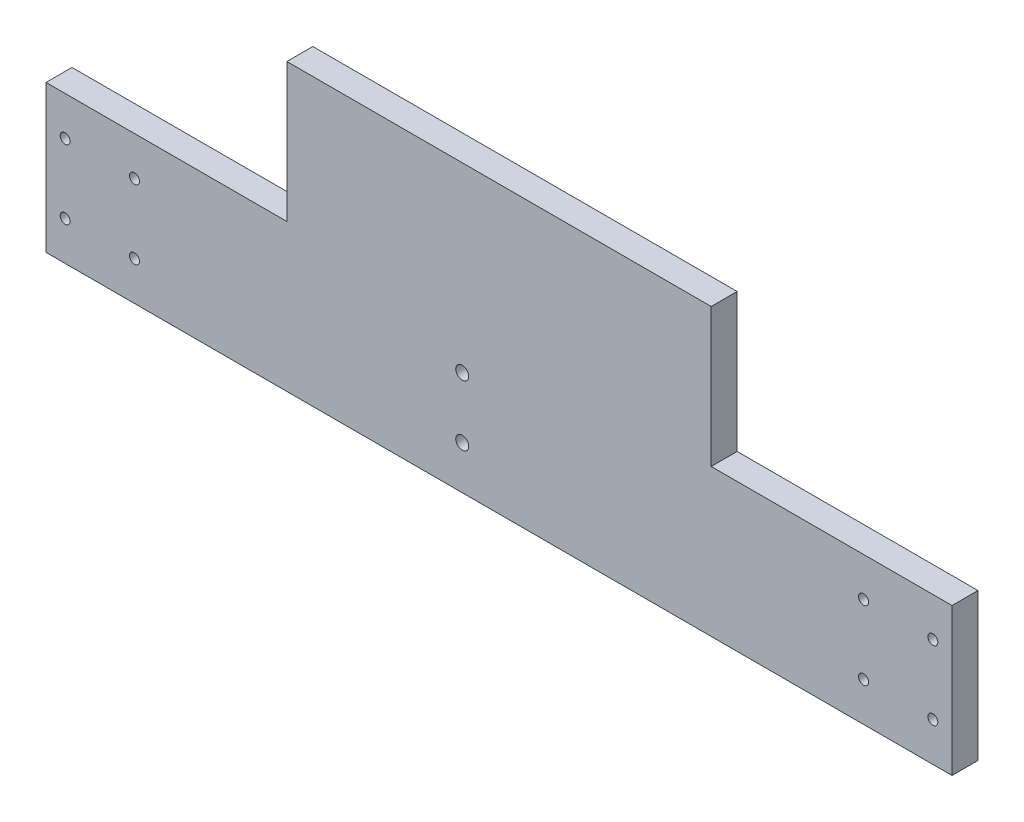
SolidWorks part; units mm, degrees
ref_plane "Plan de face" through (0, 0, 0) normal (0, 0, 1) x (1, 0, 0)
ref_plane "Plan de dessus" through (0, 0, 0) normal (0, 1, 0) x (1, 0, 0)
ref_plane "Plan de droite" through (0, 0, 0) normal (1, 0, 0) x (0, 0, -1)
sketch "Esquisse1" plane through (0, 0, 0) normal (0, 0, 1) x (1, 0, 0)
  line L0 (-104.63, 17) -> (-49, 17)
  line L1 (104.63, 17) -> (49, 17)
  line L2 (-104.63, 17) -> (-104.63, -17)
  line L3 (-104.63, -17) -> (104.63, -17)
  line L4 (104.63, 17) -> (104.63, -17)
  line L6 (-49, 17) -> (-49, 49)
  line L7 (-49, 49) -> (49, 49)
  line L8 (49, 17) -> (49, 49)
  dimension "D1" = 209.26
  dimension "D2" = 34
  dimension "D3" = 104.63
  dimension "D4" = 34
  dimension "D5" = 32
  dimension "D6" = 98
  dimension "D7" = 55.63
  dimension "D8" = 55.63
extrude "Boss.-Extru.1" add sketch "Esquisse1" along normal blind 6
sketch "Esquisse2" plane through (0, 0, 6) normal (0, 0, 1) x (1, 0, 0)
  line L0 (0, 49.0616) -> (0, -42.9956) construction
  line L1 (-104.63, 17) -> (-104.63, -17) construction
  line L3 (-104.63, -17) -> (104.63, -17) construction
  line L4 (-49, 17) -> (-104.63, 17) construction
  line L5 (-104.63, 17) -> (-104.63, -17) construction
  circle A0 centre (-100.2, 8) radius 1.15
  circle A1 centre (-84.2, 8) radius 1.15
  circle A2 centre (-84.2, -8) radius 1.15
  circle A3 centre (-100.2, -8) radius 1.15
  circle A4 centre (100.2, -8) radius 1.15
  circle A5 centre (84.2, -8) radius 1.15
  circle A6 centre (84.2, 8) radius 1.15
  circle A7 centre (100.2, 8) radius 1.15
  circle A8 centre (-8.5, 7) radius 1.5
  circle A9 centre (-8.5, -7) radius 1.5
  dimension "D1" = 2.3
  dimension "D2" = 2.3
  dimension "D3" = 2.3
  dimension "D4" = 2.3
  dimension "D12" = 3
  dimension "D14" = 3
  dimension "D5" = 4.43
  dimension "D6" = 9
  dimension "D7" = 9
  dimension "D8" = 16
  dimension "D9" = 16
  dimension "D10" = 16
  dimension "D11" = 16
  dimension "D13" = 10
  dimension "D15" = 10
  dimension "D16" = 14
  dimension "D17" = 8.5
  dimension "D18" = 4.43
extrude "Enlèv. mat.-Extru.1" cut sketch "Esquisse2" against normal blind 6
